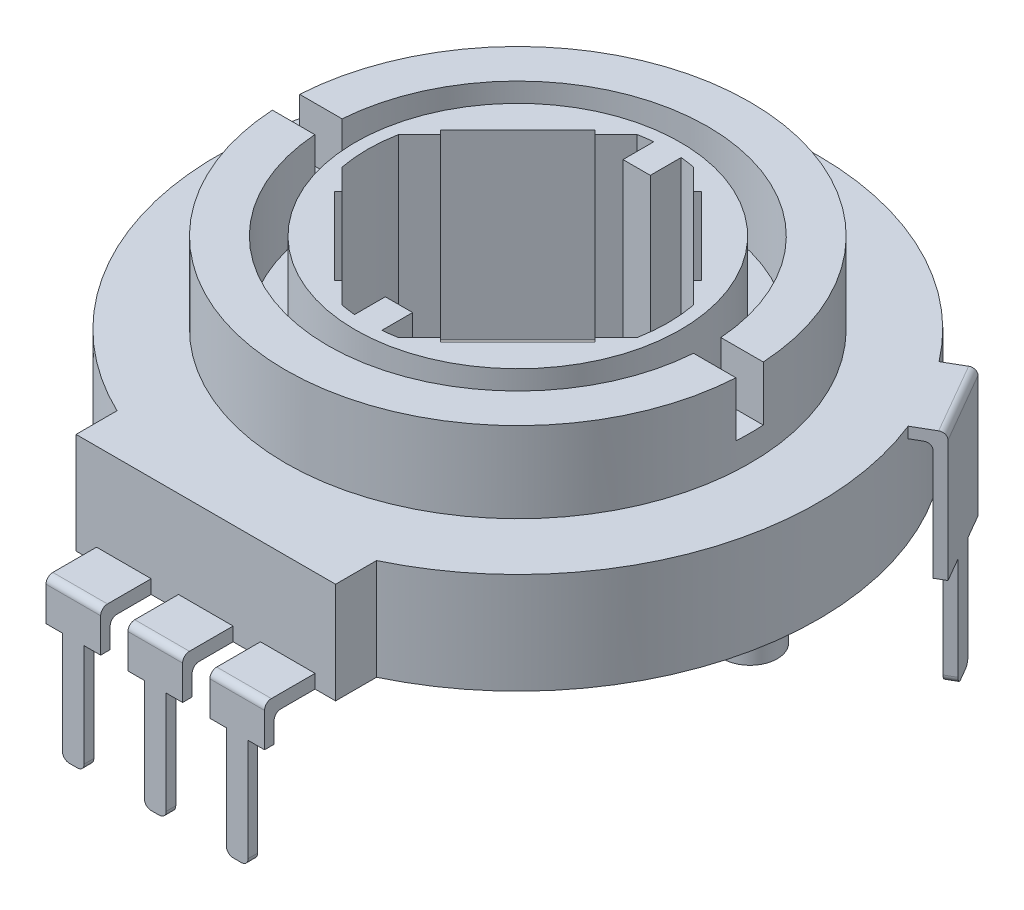
SolidWorks part; units mm, degrees
other "Markup1"
sketch "Sketch15" plane through (-11.1432, 13.7, 0.175) normal (0, 1, 0) x (1, 0, 0)
ref_plane "Front Plane" through (0, 0, 0) normal (0, 0, 1) x (1, 0, 0)
ref_plane "Top Plane" through (0, 0, 0) normal (0, 1, 0) x (1, 0, 0)
ref_plane "Right Plane" through (0, 0, 0) normal (1, 0, 0) x (0, 0, -1)
sketch "Sketch1" plane through (0, 0, 0) normal (0, 1, 0) x (1, 0, 0)
  line L1 (9.7968, 19.233) -> (10.1432, 19.433)
  line L2 (-3.4, 0.175) -> (-2.6, 0.175)
  line L3 (-3.4, 0.175) -> (-3.4, -0.175)
  line L4 (-3.4, -0.175) -> (-2.6, -0.175)
  line L5 (-2.6, 0.175) -> (-2.6, -0.175)
  line L6 (-0.4, 0.175) -> (0.4, 0.175)
  line L7 (-0.4, 0.175) -> (-0.4, -0.175)
  line L8 (-0.4, -0.175) -> (0.4, -0.175)
  line L9 (0.4, 0.175) -> (0.4, -0.175)
  line L13 (2.6, 0.175) -> (3.4, 0.175)
  line L14 (2.6, 0.175) -> (2.6, -0.175)
  line L15 (2.6, -0.175) -> (3.4, -0.175)
  line L16 (3.4, 0.175) -> (3.4, -0.175)
  line L17 (9.7968, 19.233) -> (10.2968, 18.367)
  line L18 (10.1432, 19.433) -> (10.6432, 18.567)
  line L19 (10.2968, 18.367) -> (10.6432, 18.567)
  line L20 (9.7968, 19.233) -> (10.6432, 18.567) construction
  line L21 (10.1432, 19.433) -> (10.2968, 18.367) construction
  line L22 (0, -0.175) -> (0, 22.1023) construction
  line L23 (-10.1432, 19.433) -> (-10.2968, 18.367) construction
  line L24 (-9.7968, 19.233) -> (-10.6432, 18.567) construction
  line L25 (-10.2968, 18.367) -> (-10.6432, 18.567)
  line L26 (-10.1432, 19.433) -> (-10.6432, 18.567)
  line L27 (-9.7968, 19.233) -> (-10.2968, 18.367)
  line L28 (-9.7968, 19.233) -> (-10.1432, 19.433)
  point P2 (-0.4, 0)
  point P13 (0, -0.175)
  point P14 (-2.6, 0)
  point P15 (2.6, 0)
  point P16 (-3, -0.175)
  point P17 (3, -0.175)
  point P19 (10.22, 18.9)
  point P30 (-10.22, 18.9)
  dimension "D1" = 0.8
  dimension "D2" = 0.35
  dimension "D3" = 6
  dimension "D4" = 3
  dimension "D5" = 0.4
  dimension "D6" = 1
  dimension "D7" = 18.9
  dimension "D8" = 10.22
  dimension "D9" = 30
extrude "Boss-Extrude1" add sketch "Sketch1" along normal blind 4
sketch "Sketch2" plane through (0, 4, 0) normal (0, 1, 0) x (1, 0, 0)
  line L0 (-0.4, -0.175) -> (0.4, -0.175) construction
  line L1 (-1, 0.175) -> (1, 0.175)
  line L2 (-1, 0.175) -> (-1, -0.175)
  line L3 (-1, -0.175) -> (1, -0.175)
  line L4 (1, 0.175) -> (1, -0.175)
  line L5 (-1, 0.175) -> (1, -0.175) construction
  line L6 (-1, -0.175) -> (1, 0.175) construction
  line L7 (2, 0.175) -> (2, -0.175)
  line L12 (2, 0.175) -> (4, 0.175)
  line L13 (4, 0.175) -> (4, -0.175)
  line L14 (2, -0.175) -> (4, -0.175)
  line L15 (-1, 0.175) -> (-1, -0.175)
  line L16 (-1, 0.175) -> (1, 0.175)
  line L17 (1, 0.175) -> (1, -0.175)
  line L18 (-1, -0.175) -> (1, -0.175)
  line L19 (-4, 0.175) -> (-4, -0.175)
  line L20 (-4, 0.175) -> (-2, 0.175)
  line L21 (-2, 0.175) -> (-2, -0.175)
  line L22 (-4, -0.175) -> (-2, -0.175)
  line L53 (8.4308, 19.599) -> (9.9308, 17.001)
  line L54 (12.0092, 18.201) -> (10.5092, 20.799)
  line L55 (9.9308, 17.001) -> (12.0092, 18.201)
  line L56 (10.5092, 20.799) -> (8.4308, 19.599)
  line L59 (10.7968, 17.501) -> (11.1432, 17.701)
  line L60 (9.6432, 20.299) -> (9.2968, 20.099)
  line L61 (-11.1432, 17.701) -> (-9.6432, 20.299)
  line L62 (-10.1432, 19.433) -> (-10.6432, 18.567) construction
  line L63 (-10.7968, 17.501) -> (-9.2968, 20.099)
  line L64 (-10.2968, 18.367) -> (-9.7968, 19.233) construction
  line L65 (-8.4308, 19.599) -> (-10.5092, 20.799)
  line L66 (-10.5092, 20.799) -> (-12.0092, 18.201)
  line L67 (-12.0092, 18.201) -> (-9.9308, 17.001)
  line L68 (-9.9308, 17.001) -> (-8.4308, 19.599)
  line L69 (-9.2968, 20.099) -> (-9.6432, 20.299)
  line L71 (-11.1432, 17.701) -> (-10.7968, 17.501)
  line L73 (9.2968, 20.099) -> (10.7968, 17.501)
  line L74 (9.7968, 19.233) -> (10.2968, 18.367) construction
  line L76 (9.6432, 20.299) -> (11.1432, 17.701)
  line L77 (10.6432, 18.567) -> (10.1432, 19.433) construction
  point P0 (0, 0)
  line M21 (-0.4, 0.175) -> (-0.4, -0.175)
  line M22 (-0.4, -0.175) -> (0.4, -0.175)
  line M23 (0.4, -0.175) -> (0.4, 0.175)
  line M24 (0.4, 0.175) -> (-0.4, 0.175)
  dimension "D1" = 2
  dimension "D4" = 1
  dimension "D5" = 1
  dimension "D2" = 2
  dimension "D3" = 2
extrude "Boss-Extrude2" add sketch "Sketch2" along normal blind 1.5 contours L61 L71 L63 L69 | L76 L60 L73 L59 | L4 L1 L3 M23 | M24 M21 M22 M23 | L2 L3 L1 M21 | L19 L22 L21 L20 | L7 L14 L13 L12 region at (-0.7, 4, 0) region at (0, 4, 0) region at (0.7, 4, 0) region at (3, 4, 0) region at (-3, 4, 0) region at (10.22, 4, -18.9) region at (-10.22, 4, -18.9)
sketch "Sketch3" plane through (0, 0, -0.175) normal (0, 0, -1) x (-1, 0, 0)
  line L0 (-2, 5.5) -> (-2, 4) construction
  line L1 (-4, 5.5) -> (-2, 5.5)
  line L2 (-4, 5.5) -> (-4, 5)
  line L3 (-4, 5) -> (-2, 5)
  line L4 (-2, 5.5) -> (-2, 5)
  line L5 (-1, 5.5) -> (-1, 5)
  line L6 (-1, 5.5) -> (1, 5.5)
  line L7 (1, 5.5) -> (1, 5)
  line L8 (-1, 5) -> (1, 5)
  line L9 (2, 5.5) -> (2, 5)
  line L10 (2, 5.5) -> (4, 5.5)
  line L11 (4, 5.5) -> (4, 5)
  line L12 (2, 5) -> (4, 5)
  dimension "D1" = 0.5
  dimension "D2" = 3
extrude "Boss-Extrude3" add sketch "Sketch3" along normal blind 1.5
sketch "Sketch4" plane through (0, 5, 0) normal (0, -1, 0) x (1, 0, 0)
  line L0 (2, -1.675) -> (4, -1.675) construction
  line L1 (-4.75, -1.675) -> (4.75, -1.675)
  line L2 (-4.75, -1.675) -> (-4.75, -3.175)
  line L4 (4.75, -1.675) -> (4.75, -3.175)
  arc A0 (-4.75, -3.175) -> (4.75, -3.175) centre (0, -13.0966) ccw
  dimension "D3" = 22
  dimension "D1" = 9.5
  dimension "D2" = 1.5
extrude "Boss-Extrude4" add sketch "Sketch4" against normal blind 3.7
sketch "Sketch6" plane through (0, 5.5, 0) normal (0, 1, 0) x (1, 0, 0)
  line L4 (-9.6432, 20.299) -> (-11.1432, 17.701)
  line L5 (-11.1432, 17.701) -> (-10.7968, 17.501)
  line L6 (-10.7968, 17.501) -> (-9.2968, 20.099)
  line L7 (-9.2968, 20.099) -> (-9.6432, 20.299)
  line L8 (-9.6432, 20.299) -> (-11.1432, 17.701)
  line L9 (-11.1432, 17.701) -> (-10.7968, 17.501)
  line L10 (-10.7968, 17.501) -> (-9.2968, 20.099)
  line L11 (-9.2968, 20.099) -> (-9.6432, 20.299)
  line L12 (11.1432, 17.701) -> (9.6432, 20.299)
  line L13 (9.6432, 20.299) -> (9.2968, 20.099)
  line L14 (9.2968, 20.099) -> (10.7968, 17.501)
  line L15 (10.7968, 17.501) -> (11.1432, 17.701)
  line L16 (11.1432, 17.701) -> (9.6432, 20.299)
  line L17 (9.6432, 20.299) -> (9.2968, 20.099)
  line L18 (9.2968, 20.099) -> (10.7968, 17.501)
  line L19 (10.7968, 17.501) -> (11.1432, 17.701)
  dimension "D1" = 0
  dimension "D2" = 0
extrude "Boss-Extrude6" add sketch "Sketch6" along normal up to surface (3.2 mm away) up to face at (0, 8.7, -7.6554)
sketch "Sketch7" plane through (15.6757, 0, -9.0504) normal (-0.866, 0, 0.5) x (0.5, 0, 0.866)
  line L0 (-9.7579, 8.7) -> (-9.7579, 4) construction
  line L1 (-12.7579, 8.7) -> (-9.7579, 8.7)
  line L2 (-12.7579, 8.7) -> (-12.7579, 8.3)
  line L3 (-12.7579, 8.3) -> (-9.7579, 8.3)
  line L4 (-9.7579, 8.7) -> (-9.7579, 8.3)
  dimension "D1" = 0.4
extrude "Boss-Extrude7" add sketch "Sketch7" along normal up to next
sketch "Sketch8" plane through (-15.6757, 0, -9.0504) normal (0.866, 0, 0.5) x (0.5, 0, -0.866)
  line L0 (12.7579, 8.7) -> (12.7579, 4) construction
  line L1 (9.7579, 8.7) -> (12.7579, 8.7)
  line L2 (9.7579, 8.7) -> (9.7579, 8.3)
  line L3 (9.7579, 8.3) -> (12.7579, 8.3)
  line L4 (12.7579, 8.7) -> (12.7579, 8.3)
  dimension "D1" = 0.4
extrude "Boss-Extrude8" add sketch "Sketch8" along normal up to next
sketch "Sketch9" plane through (0, 5, 0) normal (0, -1, 0) x (1, 0, 0)
  line L0 (-11, -13.0966) -> (11, -13.0966) construction
  circle A0 centre (-8.5, -13.0966) radius 1
  circle A1 centre (8.5, -13.0966) radius 1
  arc A2 (-4.75, -3.175) -> (4.75, -3.175) centre (0, -13.0966) ccw construction
  point P13 (0, -13.0966)
  dimension "D2" = 2
  dimension "D3" = 2
  dimension "D1" = 17
  dimension "D4" = 8.5
extrude "Boss-Extrude9" add sketch "Sketch9" along normal blind 2
sketch "Sketch5" plane through (0, 8.7, 0) normal (0, 1, 0) x (1, 0, 0)
  circle A0 centre (0, 13.0966) radius 8.5
  dimension "D1" = 17
extrude "Boss-Extrude5" add sketch "Sketch5" along normal blind 4.952
fillet "Fillet1" radius 0.25 10 edges at (-10.3932, 8.7, -19) (-10.0468, 8.3, -18.8) (10.0468, 8.3, -18.8) (10.3932, 8.7, -19) (-3, 5, -0.175) (0, 5, -0.175) (3, 5, -0.175) (3, 5.5, 0.175) (0, 5.5, 0.175) (-3, 5.5, 0.175)
fillet "Fillet2" radius 0.25 10 edges at (2.6, 0, 0) (3.4, 0, 0) (-3.4, 0, 0) (-2.6, 0, 0) (-0.4, 0, 0) (0.4, 0, 0) (9.97, 0, -19.333) (10.47, 0, -18.467) (-9.97, 0, -19.333) (-10.47, 0, -18.467)
sketch "Sketch10" plane through (0, 13.652, 0) normal (0, 1, 0) x (1, 0, 0)
  circle A0 centre (0, 13.0966) radius 5.5
  dimension "D1" = 11
extrude "Cut-Extrude1" cut sketch "Sketch10" against normal blind 2
sketch "Sketch11" plane through (0, 11.652, 0) normal (0, 1, 0) x (1, 0, 0)
  line L0 (-5.3193, 14.4948) -> (-1.3982, 18.4159)
  line L1 (-5.3193, 11.6984) -> (-1.3982, 7.7773)
  line L2 (1.3982, 18.4159) -> (5.3193, 14.4948)
  line L3 (1.3982, 7.7773) -> (5.3193, 11.6984)
  line L4 (-5.5, 13.0966) -> (5.5, 13.0966) construction
  line L6 (5.5, 13.0966) -> (-5.5, 13.0966) construction
  line L9 (-0.5, 7.6193) -> (-0.5, 8.7466)
  line L10 (-0.5, 8.7466) -> (0.5, 8.7466)
  line L11 (0.5, 7.6193) -> (0.5, 8.7466)
  line L15 (-0.5, 18.5738) -> (-0.5, 17.4466)
  line L16 (-0.5, 17.4466) -> (0.5, 17.4466)
  line L17 (0.5, 18.5738) -> (0.5, 17.4466)
  arc A0 (-1.3982, 7.7773) -> (-0.5, 7.6193) centre (0, 13.0966) ccw
  circle A1 centre (0, 13.0966) radius 5.5 construction
  circle A2 centre (0, 13.0966) radius 5.5 construction
  arc A3 (-5.3193, 14.4948) -> (-5.3193, 11.6984) centre (0, 13.0966) ccw
  arc A4 (5.3193, 11.6984) -> (5.3193, 14.4948) centre (0, 13.0966) ccw
  arc A5 (1.3982, 18.4159) -> (0.5, 18.5738) centre (0, 13.0966) ccw
  arc A6 (0.5, 7.6193) -> (1.3982, 7.7773) centre (0, 13.0966) ccw
  arc A7 (-0.5, 18.5738) -> (-1.3982, 18.4159) centre (0, 13.0966) ccw
  point P1 (0, 13.0966)
  point P20 (0, 8.7466)
  point P24 (0, 17.4466)
  dimension "D1" = 5.5453
  dimension "D2" = 1.3982
  dimension "D3" = 8.7
  dimension "D4" = 1
extrude "Cut-Extrude2" cut sketch "Sketch11" against normal through all
sketch "Sketch12" plane through (0, 13.652, 0) normal (0, 1, 0) x (1, 0, 0)
  line L0 (-2.2086, 18.1336) -> (-1.8031, 17.7281)
  line L1 (-1.8031, 17.7281) -> (-1.0324, 18.4988)
  line L2 (5.0371, 10.8879) -> (4.6315, 11.2934) construction
  line L3 (4.6315, 11.2934) -> (5.4022, 12.0641) construction
  line L4 (1.3982, 7.7773) -> (5.3193, 11.6984) construction
  line L5 (-1.3982, 18.4159) -> (-5.3193, 14.4948) construction
  line L6 (-5.0371, 15.3052) -> (-4.6315, 14.8997)
  line L7 (-4.6315, 14.8997) -> (-5.4022, 14.129)
  arc A0 (-1.3982, 18.4159) -> (-5.3193, 14.4948) centre (0, 13.0966) ccw construction
  circle A1 centre (0, 13.0966) radius 5.5 construction
  arc A3 (1.3982, 7.7773) -> (5.3193, 11.6984) centre (0, 13.0966) ccw construction
  arc A8 (-1.0324, 18.4988) -> (-2.2086, 18.1336) centre (0, 13.0966) ccw
  arc A9 (-5.0371, 15.3052) -> (-5.4022, 14.129) centre (0, 13.0966) ccw
  point P5 (-2.0059, 17.9309)
  dimension "D1" = 9.1
  dimension "D2" = 4
extrude "Boss-Extrude10" add sketch "Sketch12" against normal up to surface (8.652 mm away) up to face at (0, 5, -13.0966)
ref_axis "Axis1" through (0, 13.652, -13.0966) along (0, -1, 0)
pattern_circular "CirPattern2" count 4 over 360 about axis through (0, 13.652, -13.0966) along (0, 1, 0) of "Boss-Extrude10"
sketch "Sketch13" plane through (0, 13.652, 0) normal (0, 1, 0) x (1, 0, 0)
  circle A0 centre (0, 13.0966) radius 8.5 construction
  circle A1 centre (0, 13.0966) radius 5.95
  circle A3 centre (0, 13.0966) radius 6.95
  dimension "D1" = 13.9
  dimension "D2" = 1
extrude "Cut-Extrude3" cut sketch "Sketch13" against normal up to surface (4.952 mm away) up to face at (0, 8.7, -4.5966)
chamfer "Chamfer1" distance 1 angle 45 1 edges at (0, 13.652, -4.5966)
ref_plane "Plane1" through (8.5, 0, 0) normal (1, 0, 0) x (0, 0, -1)
sketch "Sketch14" plane through (8.5, 0, 0) normal (1, 0, 0) x (0, 0, -1)
  line L0 (13.0966, 13.652) -> (13.0966, 2.8232) construction
  line L1 (20.5966, 13.652) -> (5.5966, 13.652) construction
  line L2 (10.5966, 13.652) -> (12.5966, 11.652)
  line L3 (10.8879, 13.652) -> (8.0595, 13.652) construction
  line L4 (12.5966, 11.652) -> (12.5966, 9.652)
  line L5 (12.5966, 9.652) -> (13.5966, 9.652)
  line L6 (13.5966, 9.652) -> (13.5966, 11.652)
  line L7 (13.5966, 11.652) -> (15.5966, 13.652)
  line L8 (15.5966, 13.652) -> (10.5966, 13.652)
  point P10 (13.0966, 9.652)
  dimension "D1" = 1
  dimension "D2" = 135
  dimension "D3" = 135
  dimension "D4" = 2
  dimension "D5" = 4
extrude "Cut-Extrude4" cut sketch "Sketch14" against normal up to surface (1.568 mm away) up to face at (0, 13.652, -6.1466)
ref_plane "Plane2" through (-8.5, 0, 0) normal (-1, 0, 0) x (0, 0, 1)
extrude "Cut-Extrude5" cut sketch "Sketch14<2>" along normal up to surface (1.568 mm away) from surface up to face at (4.5715, 11.6576, -13.0966) starting at plane "Plane2"
sketch "Sketch14<2>" plane through (8.5, 0, 0) normal (1, 0, 0) x (0, 0, -1) same geometry as "Sketch14"
sketch "Sketch16" plane through (0, 13.652, 0) normal (0, 1, 0) x (1, 0, 0)
  circle A0 centre (0, 13.0966) radius 8.5
extrude "Cut-Extrude6" cut sketch "Sketch16" against normal up to vertex (2 mm away) up to point (-8.4853, 11.652, -13.5966)
